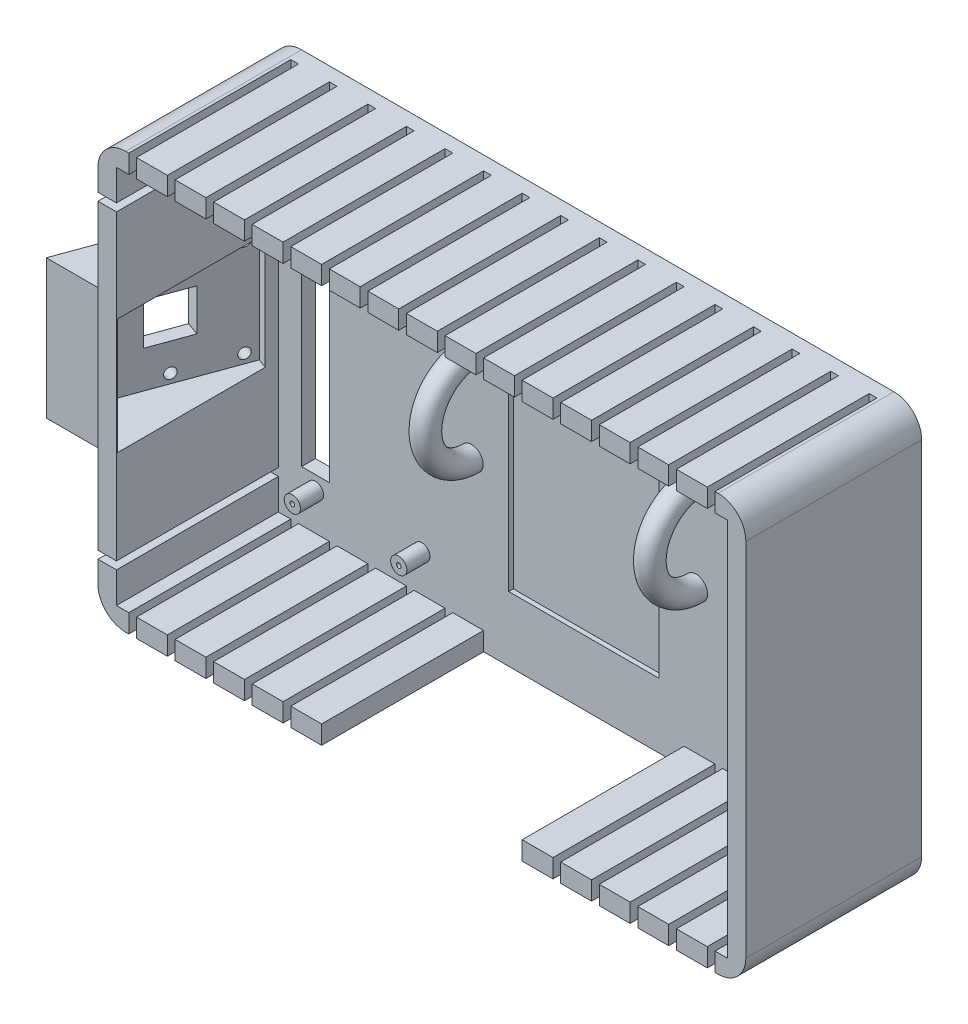
SolidWorks part; units mm, degrees
ref_plane "Front Plane" through (0, 0, 0) normal (1, 0, 0) x (0, 1, 0)
ref_plane "Top Plane" through (0, 0, 0) normal (0, 0, 1) x (0, 1, 0)
ref_plane "Right Plane" through (0, 0, 0) normal (0, 1, 0) x (-1, 0, 0)
sketch "Sketch1" plane through (0, 0, 0) normal (0, 0, 1) x (0, 1, 0)
  line L0 (-45, 0) -> (45, 0) construction
  line L1 (45, -70) -> (-45, -70)
  line L2 (45, -70) -> (45, 70)
  line L3 (45, 70) -> (-45, 70)
  line L4 (-45, -70) -> (-45, 70)
  line L5 (0, 70) -> (0, -70) construction
  point P9 (0, 0)
  dimension "D1" = 140
  dimension "D2" = 90
extrude "Boss-Extrude1" add sketch "Sketch1" along normal blind 3
sketch "Sketch2" plane through (0, 0, 3) normal (0, 0, 1) x (1, 0, 0)
  line L0 (-70, 45) -> (-70, -45) construction
  line L1 (-16.25, 31) -> (16.25, 31)
  line L2 (-16.25, 31) -> (-16.25, -31)
  line L3 (-16.25, -31) -> (16.25, -31)
  line L4 (16.25, 31) -> (16.25, -31)
  line L6 (-70, 0) -> (-16.25, 0) construction
  line L7 (16.25, 0) -> (70, 0) construction
  line L8 (70, -45) -> (70, 45) construction
  line L9 (0, 31) -> (0, 45) construction
  line L10 (70, 45) -> (-70, 45) construction
  line L11 (0, -31) -> (0, -45) construction
  line L12 (-70, -45) -> (70, -45) construction
  dimension "D1" = 62
  dimension "D2" = 32.5
extrude "Cut-Extrude1" cut sketch "Sketch2" against normal blind 1
sketch "Sketch6" plane through (0, 0, 3) normal (0, 0, 1) x (1, 0, 0)
  line L0 (-70, -45) -> (70, -45) construction
  line L2 (-58, 25) -> (-58, 45) construction
  line L3 (70, 45) -> (-70, 45) construction
  circle A0 centre (-58, 25) radius 1.75
  circle A1 centre (-35, 25) radius 1.75
  circle A2 centre (-35, -33) radius 1.75
  circle A3 centre (-58, -33) radius 1.75
  circle A4 centre (-58, 25) radius 0.5
  circle A5 centre (-35, 25) radius 0.5
  circle A6 centre (-58, -33) radius 0.5
  circle A7 centre (-35, -33) radius 0.5
  dimension "D1" = 3.5
  dimension "D2" = 23
  dimension "D3" = 58
  dimension "D4" = 12
  dimension "D5" = 1
extrude "Boss-Extrude2" add sketch "Sketch6" along normal blind 5 contours A1 | A0 | A3 | A2 region at (-59.7005, 25, 3) region at (-36.7005, 25, 3) region at (-36.7005, -33, 3) region at (-59.7005, -33, 3)
extrude "Boss-Extrude3" add sketch "Sketch6<3>" along normal blind 4 contours A4 | A5 | A6 | A7 region at (-58, 25, 3) region at (-35, 25, 3) region at (-58, -33, 3) region at (-35, -33, 3)
sketch "Sketch6<3>" plane through (0, 0, 3) normal (0, 0, 1) x (1, 0, 0) same geometry as "Sketch6"
sketch "Sketch7" plane through (0, 0, 3) normal (0, 0, 1) x (1, 0, 0)
  line L0 (-61.6667, 45) -> (-61.6667, 41)
  line L1 (-70, 45) -> (-63.3333, 45)
  line L2 (-70, 45) -> (-70, 41)
  line L3 (-70, 41) -> (-63.3333, 41)
  line L4 (-63.3333, 45) -> (-63.3333, 41)
  line L5 (-61.6667, 45) -> (-55, 45)
  line L6 (-55, 45) -> (-55, 41)
  line L7 (-61.6667, 41) -> (-55, 41)
  line L8 (-53.3333, 45) -> (-53.3333, 41)
  line L9 (-53.3333, 45) -> (-46.6667, 45)
  line L10 (-46.6667, 45) -> (-46.6667, 41)
  line L11 (-53.3333, 41) -> (-46.6667, 41)
  line L12 (-45, 45) -> (-45, 41)
  line L13 (-45, 45) -> (-38.3333, 45)
  line L14 (-38.3333, 45) -> (-38.3333, 41)
  line L15 (-45, 41) -> (-38.3333, 41)
  line L16 (-36.6667, 45) -> (-36.6667, 41)
  line L17 (-36.6667, 45) -> (-30, 45)
  line L18 (-30, 45) -> (-30, 41)
  line L19 (-36.6667, 41) -> (-30, 41)
  line L20 (-28.3333, 45) -> (-28.3333, 41)
  line L21 (-28.3333, 45) -> (-21.6667, 45)
  line L22 (-21.6667, 45) -> (-21.6667, 41)
  line L23 (-28.3333, 41) -> (-21.6667, 41)
  line L24 (-20, 45) -> (-20, 41)
  line L25 (-20, 45) -> (-13.3333, 45)
  line L26 (-13.3333, 45) -> (-13.3333, 41)
  line L27 (-20, 41) -> (-13.3333, 41)
  line L28 (-11.6667, 45) -> (-11.6667, 41)
  line L29 (-11.6667, 45) -> (-5, 45)
  line L30 (-5, 45) -> (-5, 41)
  line L31 (-11.6667, 41) -> (-5, 41)
  line L32 (-3.3333, 45) -> (-3.3333, 41)
  line L33 (-3.3333, 45) -> (3.3333, 45)
  line L34 (3.3333, 45) -> (3.3333, 41)
  line L35 (-3.3333, 41) -> (3.3333, 41)
  line L36 (5, 45) -> (5, 41)
  line L37 (5, 45) -> (11.6667, 45)
  line L38 (11.6667, 45) -> (11.6667, 41)
  line L39 (5, 41) -> (11.6667, 41)
  line L40 (13.3333, 45) -> (13.3333, 41)
  line L41 (13.3333, 45) -> (20, 45)
  line L42 (20, 45) -> (20, 41)
  line L43 (13.3333, 41) -> (20, 41)
  line L44 (21.6667, 45) -> (21.6667, 41)
  line L45 (21.6667, 45) -> (28.3333, 45)
  line L46 (28.3333, 45) -> (28.3333, 41)
  line L47 (21.6667, 41) -> (28.3333, 41)
  line L48 (30, 45) -> (30, 41)
  line L49 (30, 45) -> (36.6667, 45)
  line L50 (36.6667, 45) -> (36.6667, 41)
  line L51 (30, 41) -> (36.6667, 41)
  line L52 (38.3333, 45) -> (38.3333, 41)
  line L53 (38.3333, 45) -> (45, 45)
  line L54 (45, 45) -> (45, 41)
  line L55 (38.3333, 41) -> (45, 41)
  line L56 (46.6667, 45) -> (46.6667, 41)
  line L57 (46.6667, 45) -> (53.3333, 45)
  line L58 (53.3333, 45) -> (53.3333, 41)
  line L59 (46.6667, 41) -> (53.3333, 41)
  line L60 (55, 45) -> (55, 41)
  line L61 (55, 45) -> (61.6667, 45)
  line L62 (61.6667, 45) -> (61.6667, 41)
  line L63 (55, 41) -> (61.6667, 41)
  line L64 (63.3333, 45) -> (63.3333, 41)
  line L65 (63.3333, 45) -> (70, 45)
  line L66 (70, 45) -> (70, 41)
  line L67 (63.3333, 41) -> (70, 41)
  line L112 (0, 0) -> (0, 18.2112) construction
  line L113 (0, 0) -> (-20.7335, 0) construction
  line L114 (13.3333, -45) -> (20, -45)
  line L115 (20, -45) -> (20, -41)
  line L116 (13.3333, -41) -> (20, -41)
  line L117 (13.3333, -45) -> (13.3333, -41)
  line L118 (21.6667, -45) -> (28.3333, -45)
  line L119 (28.3333, -45) -> (28.3333, -41)
  line L120 (21.6667, -41) -> (28.3333, -41)
  line L121 (21.6667, -45) -> (21.6667, -41)
  line L122 (30, -45) -> (36.6667, -45)
  line L123 (36.6667, -45) -> (36.6667, -41)
  line L124 (30, -41) -> (36.6667, -41)
  line L125 (30, -45) -> (30, -41)
  line L126 (38.3333, -45) -> (45, -45)
  line L127 (45, -45) -> (45, -41)
  line L128 (38.3333, -41) -> (45, -41)
  line L129 (38.3333, -45) -> (38.3333, -41)
  line L130 (46.6667, -45) -> (53.3333, -45)
  line L131 (53.3333, -45) -> (53.3333, -41)
  line L132 (46.6667, -41) -> (53.3333, -41)
  line L133 (46.6667, -45) -> (46.6667, -41)
  line L134 (55, -45) -> (61.6667, -45)
  line L135 (61.6667, -45) -> (61.6667, -41)
  line L136 (55, -41) -> (61.6667, -41)
  line L137 (55, -45) -> (55, -41)
  line L138 (63.3333, -45) -> (70, -45)
  line L139 (70, -45) -> (70, -41)
  line L140 (63.3333, -41) -> (70, -41)
  line L141 (63.3333, -45) -> (63.3333, -41)
  line L142 (5, -45) -> (11.6667, -45)
  line L143 (11.6667, -45) -> (11.6667, -41)
  line L144 (5, -41) -> (11.6667, -41)
  line L145 (5, -45) -> (5, -41)
  line L146 (-3.3333, -45) -> (3.3333, -45)
  line L147 (3.3333, -45) -> (3.3333, -41)
  line L148 (-3.3333, -41) -> (3.3333, -41)
  line L149 (-3.3333, -45) -> (-3.3333, -41)
  line L150 (-11.6667, -45) -> (-5, -45)
  line L151 (-5, -45) -> (-5, -41)
  line L152 (-11.6667, -41) -> (-5, -41)
  line L153 (-11.6667, -45) -> (-11.6667, -41)
  line L154 (-20, -45) -> (-13.3333, -45)
  line L155 (-13.3333, -45) -> (-13.3333, -41)
  line L156 (-20, -41) -> (-13.3333, -41)
  line L157 (-20, -45) -> (-20, -41)
  line L158 (-28.3333, -45) -> (-21.6667, -45)
  line L159 (-21.6667, -45) -> (-21.6667, -41)
  line L160 (-28.3333, -41) -> (-21.6667, -41)
  line L161 (-28.3333, -45) -> (-28.3333, -41)
  line L162 (-36.6667, -45) -> (-30, -45)
  line L163 (-30, -45) -> (-30, -41)
  line L164 (-36.6667, -41) -> (-30, -41)
  line L165 (-36.6667, -45) -> (-36.6667, -41)
  line L166 (-70, -41) -> (-63.3333, -41)
  line L167 (-63.3333, -45) -> (-63.3333, -41)
  line L168 (-70, -45) -> (-63.3333, -45)
  line L169 (-70, -45) -> (-70, -41)
  line L170 (-61.6667, -45) -> (-55, -45)
  line L171 (-55, -45) -> (-55, -41)
  line L172 (-61.6667, -41) -> (-55, -41)
  line L173 (-61.6667, -45) -> (-61.6667, -41)
  line L174 (-53.3333, -45) -> (-46.6667, -45)
  line L175 (-46.6667, -45) -> (-46.6667, -41)
  line L176 (-53.3333, -41) -> (-46.6667, -41)
  line L177 (-53.3333, -45) -> (-53.3333, -41)
  line L178 (-45, -45) -> (-38.3333, -45)
  line L179 (-38.3333, -45) -> (-38.3333, -41)
  line L180 (-45, -41) -> (-38.3333, -41)
  line L181 (-45, -45) -> (-45, -41)
  line L226 (-70, 32.6633) -> (-60.5263, 32.6633) construction
  line L227 (-70, -32.6633) -> (-61.2912, -32.6633) construction
  line L228 (-70, 45) -> (-70, -45) construction
  line L229 (-70, 32.6633) -> (-66, 32.6633)
  line L230 (-70, 32.6633) -> (-70, -32.6633)
  line L231 (-70, -32.6633) -> (-66, -32.6633)
  line L232 (-66, 32.6633) -> (-66, -32.6633)
  line L233 (70, 45) -> (66, 45)
  line L234 (70, 45) -> (70, -45)
  line L235 (70, -45) -> (66, -45)
  line L236 (66, 45) -> (66, -45)
  line L237 (-70, 41) -> (-66, 41)
  line L238 (-70, 41) -> (-70, 34.3333)
  line L239 (-70, 34.3333) -> (-66, 34.3333)
  line L240 (-66, 41) -> (-66, 34.3333)
  line L246 (-70, -34.3333) -> (-66, -34.3333)
  line L247 (-70, -34.3333) -> (-70, -41)
  line L248 (-70, -41) -> (-66, -41)
  line L249 (-66, -34.3333) -> (-66, -41)
  line M13 (70, 45) -> (-70, 45)
  line M14 (-70, 45) -> (-70, -45)
  line M15 (-70, -45) -> (70, -45)
  line M16 (70, -45) -> (70, 45)
  dimension "D1" = 6.6667
  dimension "D2" = 4
  dimension "D6" = 1.67
  dimension "D4" = 4
  dimension "D7" = 1.67
  dimension "D3" = 17
sketch "Sketch9" plane through (0, 0, 3) normal (0, 0, 1) x (1, 0, 0)
  line L0 (-36.3093, 0) -> (22.5747, 0) construction
  line L1 (0, 0) -> (0, 22.2066) construction
  line L2 (-16.25, 31) -> (-16.25, -31) construction
  circle A0 centre (-24.25, -10) radius 2.5
  circle A1 centre (24.25, -10) radius 2.5
  dimension "D1" = 5
  dimension "D2" = 10
  dimension "D3" = 8
revolve "Revolve3" add sketch "Sketch9" angle 180 about L0 reverse direction yes
extrude "Boss-Extrude8" add sketch "Sketch7" along normal blind 35 contours L167 L166 M15 M14 | L173 L171 L172 M15 | L177 L175 L176 M15 | L181 L179 L180 M15 | L165 L163 L164 M15 | L161 L159 L160 M15 | L157 L155 L156 M15 | L153 L151 L152 M15 | L149 L147 L148 M15 | L145 L143 L144 M15 | L121 L119 L120 M15 | L125 L123 L124 M15 | L129 L127 L128 M15 | L133 L131 L132 M15 | L137 L135 L136 M15 | L140 L236 L138 M16 | L67 L236 L140 M16 | L60 L63 L62 M13 | L56 L59 L58 M13 | L48 L51 L50 M13 | L32 L35 L34 M13 | L28 L31 L30 M13 | L24 L27 L26 M13 | L20 L23 L22 M13 | L16 L19 L18 M13 | L0 L7 L6 M13 | L4 L3 M13 M14 | L240 L237 L239 M14 | L116 L115 L114 L117 | L138 L141 L140 L139 | L66 L67 L64 L65 | L53 L54 L55 L52 | L44 L47 L46 L45 | L42 L43 L40 L41 | L36 L39 L38 L37 | L28 L31 L30 L29 | L13 L14 L15 L12 | L9 L10 L11 L8 | L230 L231 L232 L229 | L247 L248 L249 L246 region at (-58.3333, 43, 3) region at (-66.6667, 43, 3) region at (-68, 37.6667, 3) region at (-33.3333, 43, 3) region at (-25, 43, 3) region at (-66.6667, -43, 3) region at (-16.6667, 43, 3) region at (-58.3333, -43, 3) region at (-8.3333, 43, 3) region at (-50, -43, 3) region at (0, 43, 3) region at (-41.6667, -43, 3) region at (-33.3333, -43, 3) region at (-25, -43, 3) region at (-16.6667, -43, 3) region at (33.3333, 43, 3) region at (-8.3333, -43, 3) region at (0, -43, 3) region at (50, 43, 3) region at (8.3333, -43, 3) region at (58.3333, 43, 3) region at (25, -43, 3) region at (68, 0, 3) region at (68, -43, 3) region at (33.3333, -43, 3) region at (41.6667, -43, 3) region at (58.3333, -43, 3) region at (50, -43, 3)
sketch "Sketch18" plane through (0, 0, 0) normal (0, 1, 0) x (-1, 0, 0)
  line L0 (70, 36.5) -> (82.6547, 36.5)
  line L1 (70, 38) -> (70, 0) construction
  line L2 (82.6547, 36.5) -> (70, 1.7314)
  line L3 (70, 1.7314) -> (70, 36.5)
  line L4 (63.3333, 38) -> (70, 38) construction
  dimension "D1" = 20
  dimension "D2" = 37
  dimension "D3" = 1.5
extrude "Boss-Extrude9" add sketch "Sketch18" along normal blind 15 and the other way blind 15
sketch "Sketch19" plane through (-61.2551, 0, -22.295) normal (-0.9397, 0, -0.342) x (0, -1, 0)
  line L0 (-10.5, 43.0684) -> (-10.5, 30.5684) construction
  line L1 (4.5, 38.5684) -> (-4.5, 38.5684)
  line L2 (4.5, 38.5684) -> (4.5, 47.5684)
  line L3 (4.5, 47.5684) -> (-4.5, 47.5684)
  line L4 (-4.5, 38.5684) -> (-4.5, 47.5684)
  line L5 (10.5, 43.0684) -> (10.5, 30.5684) construction
  line L6 (-10.5, 43.0684) -> (10.5, 43.0684) construction
  line L7 (-10.5, 30.5684) -> (10.5, 30.5684) construction
  line L8 (0, 43.0684) -> (0, 30.5684) construction
  line L9 (-15, 25.5684) -> (-15, 62.5684) construction
  line L10 (15, 25.5684) -> (15, 62.5684) construction
  line L14 (15, 25.5684) -> (-15, 25.5684) construction
  circle A0 centre (-10.5, 43.0684) radius 1.15
  circle A1 centre (10.5, 43.0684) radius 1.15
  circle A2 centre (10.5, 30.5684) radius 1.15
  circle A3 centre (-10.5, 30.5684) radius 1.15
  circle A4 centre (0, 43.0684) radius 1
  point P15 (0, 47.5684)
  point P16 (4.5, 43.0684)
  dimension "D1" = 2.3
  dimension "D3" = 21
  dimension "D4" = 12.5
  dimension "D6" = 2
  dimension "D2" = 9
  dimension "D5" = 5
extrude "Cut-Extrude2" cut sketch "Sketch19" against normal up to next contours A4 | L4 L1 L2 L3 A4 | A0 | A3 | A2 | A1 region at (-74.4898, 0, 14.067) region at (-75.9854, 10.5, 18.176) region at (-75.9854, -10.5, 18.176) region at (-71.7101, -10.5, 6.4298) region at (-71.7101, 10.5, 6.4298) region at (-75.9854, 0, 18.176)
sketch "Sketch21" plane through (-61.2551, 0, -22.295) normal (-0.9397, 0, -0.342) x (0, -1, 0)
  line L0 (0, 62.5684) -> (0, 25.5684) construction
  line L1 (-12.5, 58.0684) -> (12.5, 58.0684)
  line L2 (-12.5, 58.0684) -> (-12.5, 28.0684)
  line L3 (-12.5, 28.0684) -> (12.5, 28.0684)
  line L4 (12.5, 58.0684) -> (12.5, 28.0684)
  line L5 (15, 62.5684) -> (-15, 62.5684) construction
  line L6 (15, 25.5684) -> (-15, 25.5684) construction
  circle A0 centre (-10.5, 30.5684) radius 1.15 construction
  dimension "D3" = 2.5
  dimension "D1" = 25
  dimension "D2" = 30
extrude "Cut-Extrude5" cut sketch "Sketch21" against normal up to next from offset 3 offset against normal yes
sketch "Sketch22" plane through (0, 0, 3) normal (0, 0, 1) x (1, 0, 0)
  line L0 (-16.25, 39) -> (16.25, 39)
  line L1 (-16.25, 39) -> (-16.25, 33)
  line L2 (16.25, 39) -> (16.25, 33)
  line L3 (-16.25, 33) -> (16.25, 33)
  line L4 (-16.25, 39) -> (16.25, 33) construction
  line L5 (16.25, 39) -> (-16.25, 33) construction
  line L6 (16.25, 31) -> (-16.25, 31) construction
  line L7 (-3.3333, 45) -> (-5, 45) construction
  point P1 (0, 36)
  dimension "D1" = 6
  dimension "D2" = 6
extrude "Cut-Extrude6" cut sketch "Sketch22" against normal through all
sketch "Sketch23" plane through (0, -45, 0) normal (0, -1, 0) x (1, 0, 0)
  line L0 (-20, 38) -> (-13.3333, 38) construction
  line L5 (-20, 38) -> (20, 38)
  line L6 (-20, 38) -> (-20, 3)
  line L7 (-20, 3) -> (20, 3)
  line L8 (20, 38) -> (20, 3)
extrude "Cut-Extrude7" cut sketch "Sketch23" against normal up to next (4 mm away) contours L8 L7 L6 L5
fillet "Fillet1" radius 6 4 edges at (70, 45, 19) (70, -45, 19) (-70, -45, 19) (-70, 45, 19)
sketch "Sketch24" plane through (0, 0, 3) normal (0, 0, 1) x (1, 0, 0)
  line L0 (-61, 22) -> (-61, -30)
  line L1 (-61, 22) -> (-55, 22)
  line L2 (-61, -30) -> (-55, -30)
  line L3 (-55, 22) -> (-55, -30)
  line L4 (-61, 22) -> (-55, -30) construction
  line L5 (-61, -30) -> (-55, 22) construction
  line L6 (-58, -33) -> (-58, 25) construction
  circle A2 centre (-58, 25) radius 0.5 construction
  circle A4 centre (-58, -33) radius 0.5 construction
  point P1 (-58, -4)
  dimension "D2" = 3
  dimension "D1" = 3
  dimension "D3" = 6
extrude "Cut-Extrude8" cut sketch "Sketch24" against normal through all
sketch "Sketch25" plane through (0, 0, 0) normal (0, 0, -1) x (1, 0, 0)
  line L0 (-28.95, -27.94) -> (-28.95, 27.94)
  line L1 (-28.95, -27.94) -> (-48, -27.94)
  line L2 (-28.95, 27.94) -> (-48, 27.94)
  line L3 (-48, -27.94) -> (-48, 27.94)
  line L4 (-28.95, -27.94) -> (-48, 27.94) construction
  line L5 (-28.95, 27.94) -> (-48, -27.94) construction
  line L8 (-70, 0) -> (19.1904, 0) construction
  line L9 (-70, -39) -> (-70, 39) construction
  line L10 (-64, 45) -> (64, 45) construction
  line L11 (64, -45) -> (-64, -45) construction
  line L12 (-55, 30) -> (-55, -22) construction
  circle A0 centre (-48, 27.94) radius 0.75
  circle A1 centre (-28.95, 27.94) radius 0.75
  circle A2 centre (-28.95, -27.94) radius 0.75
  circle A3 centre (-48, -27.94) radius 0.75
  circle A4 centre (-48, 27.94) radius 1.5
  circle A5 centre (-28.95, 27.94) radius 1.5
  circle A6 centre (-48, -27.94) radius 1.5
  circle A7 centre (-28.95, -27.94) radius 1.5
  point P1 (-38.475, 0)
  dimension "D1" = 1.5
  dimension "D5" = 3
  dimension "D2" = 55.88
  dimension "D3" = 19.05
  dimension "D4" = 7
extrude "Boss-Extrude10" add sketch "Sketch25" along normal blind 5 contours L3 A4 L2 A0 | L2 A4 L3 A0 | L2 A5 L0 A1 | L0 A1 L2 | L0 A5 L2 A1 | L3 A6 L1 A3 | L0 A7 L1 A2 | L1 A7 L0 A2 | L1 A6 L3 A3 | A1 region at (-29.6927, 27.1973, 0) region at (-28.9076, 26.815, 0) region at (-29.6927, -27.1973, 0) region at (-28.9076, -26.815, 0) region at (-49.0307, 28.9707, 0) region at (-47.2573, 27.1973, 0) region at (-28.8439, -28.0461, 0) region at (-47.2573, -27.1973, 0) region at (-46.875, -27.9824, 0)
